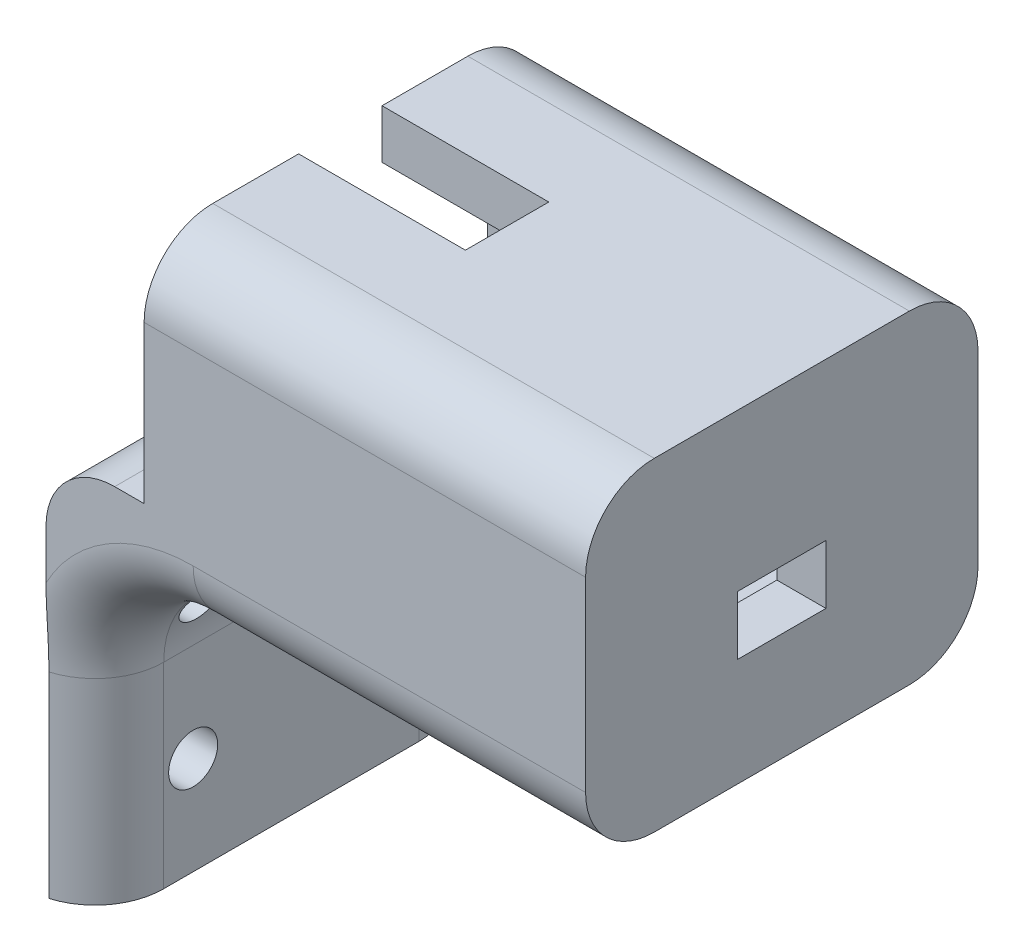
SolidWorks part; units mm, degrees
ref_plane "Front Plane" through (0, 0, 0) normal (0, 0, 1) x (1, 0, 0)
ref_plane "Top Plane" through (0, 0, 0) normal (0, 1, 0) x (1, 0, 0)
ref_plane "Right Plane" through (0, 0, 0) normal (1, 0, 0) x (0, 0, -1)
sketch "Sketch1" plane through (0, 0, 0) normal (0, 1, 0) x (1, 0, 0)
  line L1 (22.5, 20) -> (-22.5, 20)
  line L2 (22.5, 20) -> (22.5, -20)
  line L3 (22.5, -20) -> (-22.5, -20)
  line L4 (-22.5, 20) -> (-22.5, -20)
  line L5 (22.5, 20) -> (-22.5, -20) construction
  line L6 (22.5, -20) -> (-22.5, 20) construction
  point P0 (0, 0)
  dimension "D1" = 45
  dimension "D2" = 40
extrude "Boss-Extrude1" add sketch "Sketch1" along normal blind 28
sketch "Sketch5" plane through (-22.5, 0, 0) normal (-1, 0, 0) x (0, 0, 1)
  line L0 (-20, 28) -> (20, 28) construction
  line L1 (-15, 23) -> (15, 23)
  line L2 (-15, 23) -> (-15, 5)
  line L3 (-15, 5) -> (15, 5)
  line L4 (15, 23) -> (15, 5)
  line L6 (-20, 0) -> (20, 0) construction
  line L7 (20, 28) -> (20, 0) construction
  line L8 (-20, 28) -> (-20, 0) construction
  dimension "D1" = 5
  dimension "D2" = 5
  dimension "D3" = 5
  dimension "D4" = 5
extrude "Cut-Extrude2" cut sketch "Sketch5" against normal blind 40
sketch "Sketch6" plane through (-22.5, 0, 0) normal (-1, 0, 0) x (0, 0, 1)
  line L0 (15, 23) -> (-15, 23) construction
  line L1 (-4.25, 23) -> (4.25, 23)
  line L2 (-4.25, 23) -> (-4.25, 28)
  line L3 (-4.25, 28) -> (4.25, 28)
  line L4 (4.25, 23) -> (4.25, 28)
  line L5 (-20, 28) -> (20, 28) construction
  line L6 (-20, 28) -> (-20, 0) construction
  line L8 (20, 28) -> (20, 0) construction
  dimension "D1" = 15.75
  dimension "D2" = 8.5
  dimension "D3" = 15.75
extrude "Cut-Extrude3" cut sketch "Sketch6" against normal blind 17
sketch "Sketch7" plane through (22.5, 0, 0) normal (1, 0, 0) x (0, 0, -1)
  line L0 (-20, 0) -> (20, 0) construction
  line L1 (-4.5, 12) -> (4.5, 12)
  line L2 (-4.5, 12) -> (-4.5, 6)
  line L3 (-4.5, 6) -> (4.5, 6)
  line L4 (4.5, 12) -> (4.5, 6)
  line L5 (20, 28) -> (20, 0) construction
  line L6 (-20, 28) -> (-20, 0) construction
  dimension "D1" = 12
  dimension "D2" = 9
  dimension "D3" = 15.5
  dimension "D4" = 15.5
  dimension "D5" = 6
extrude "Cut-Extrude4" cut sketch "Sketch7" against normal blind 17
sketch "Sketch8" plane through (0, 0, 0) normal (0, -1, 0) x (1, 0, 0)
  line L1 (-22.5, 20) -> (22.5, 20)
  line L2 (-22.5, 20) -> (-22.5, -20)
  line L3 (-22.5, -20) -> (22.5, -20)
  line L4 (22.5, 20) -> (22.5, -20)
extrude "Boss-Extrude2" add sketch "Sketch8" along normal blind 5
sketch "Sketch9" plane through (-22.5, 0, 0) normal (-1, 0, 0) x (0, 0, 1)
  line L0 (-20, 28) -> (-20, -5) construction
  line L1 (-20, 5) -> (20, 5)
  line L2 (-20, 5) -> (-20, -5)
  line L3 (-20, -5) -> (20, -5)
  line L4 (20, 5) -> (20, -5)
extrude "Boss-Extrude3" add sketch "Sketch9" along normal blind 10
sketch "Sketch10" plane through (0, -5, 0) normal (0, -1, 0) x (1, 0, 0)
  line L0 (-32.5, -20) -> (-32.5, 20) construction
  line L1 (-32.5, 20) -> (-27.5, 20)
  line L2 (-32.5, 20) -> (-32.5, -20)
  line L3 (-32.5, -20) -> (-27.5, -20)
  line L4 (-27.5, 20) -> (-27.5, -20)
  line L5 (-32.5, -20) -> (22.5, -20) construction
  dimension "D1" = 5
extrude "Boss-Extrude4" add sketch "Sketch10" along normal blind 30
sketch "Sketch13" plane through (-32.5, 0, 0) normal (-1, 0, 0) x (0, 0, 1)
  line L0 (0, 5) -> (0, -35) construction
  line L1 (-15, 5) -> (15, 5) construction
  line L2 (20, -35) -> (-20, -35) construction
  line L3 (-20, 5) -> (-20, -35) construction
  circle A0 centre (-10, -25) radius 2.5
  circle A1 centre (-10, -10) radius 2.5
  circle A2 centre (10, -10) radius 2.5
  circle A3 centre (10, -25) radius 2.5
  dimension "D1" = 5
  dimension "D2" = 5
  dimension "D3" = 10
  dimension "D4" = 10
  dimension "D5" = 15
  dimension "D6" = 10
extrude "Cut-Extrude5" cut sketch "Sketch13" against normal blind 27
fillet "Fillet1" radius 10 1 edges at (-27.5, -5, 0)
fillet "Fillet3" radius 7 8 edges at (-27.5, -25, -20) (-24.5711, -7.9289, -20) (-27.5, -25, 20) (-24.5711, -7.9289, 20) (2.5, -5, -20) (0, 28, -20) (0, 28, 20) (2.5, -5, 20)
fillet "Fillet4" radius 7 1 edges at (-32.5, 5, 0)
